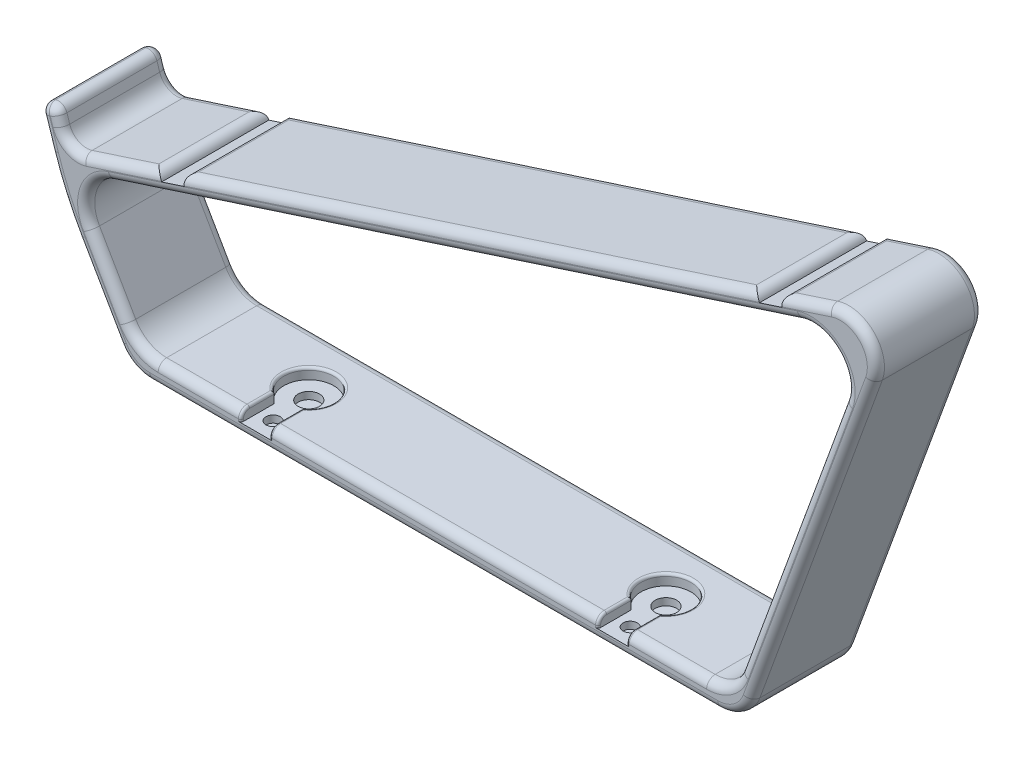
SolidWorks part; units mm, degrees
ref_plane "Front Plane" through (0, 0, 0) normal (0, 0, 1) x (1, 0, 0)
ref_plane "Top Plane" through (0, 0, 0) normal (0, 1, 0) x (1, 0, 0)
ref_plane "Right Plane" through (0, 0, 0) normal (1, 0, 0) x (0, 0, -1)
ref_axis "X Axis" through (0, 0, -132.1637) along (0, 0, 1)
ref_axis "Z Axis" through (0, -24.397, 0) along (0, 1, 0)
ref_axis "Y Axis" through (133.8141, 0, 0) along (-1, 0, 0)
sketch "Sketch13" plane through (0, 0, 0) normal (0, 0, 1) x (1, 0, 0)
  line L0 (-98.9778, 0) -> (72.8295, 0)
  line L1 (72.8295, 0) -> (116.5059, 120)
  line L2 (116.5059, 120) -> (-116.5059, 44.3)
  line L3 (-116.5059, 44.3) -> (-119.5957, 53.8107)
  line L4 (-119.5957, 53.8107) -> (-124.3511, 52.2658)
  line L5 (-124.3511, 52.2658) -> (-118.1715, 33.2444)
  line L6 (-118.1715, 33.2444) -> (-98.9778, 0)
  line L7 (-115.8657, 39.2507) -> (108.3014, 112.0773)
  line L8 (108.3014, 112.0773) -> (69.6924, 6)
  line L9 (69.6924, 6) -> (-96.6684, 6)
  line L10 (-96.6684, 6) -> (-115.8657, 39.2507)
  line L11 (-8.8901, 79.2618) -> (-7.3452, 74.5065) construction
  line L12 (92.7283, 69.2907) -> (97.4268, 67.5806) construction
  line L13 (33.746, 6) -> (33.746, 0) construction
  line L14 (-110.3349, 19.671) -> (-106.0047, 22.171) construction
  line L15 (116.5059, 120) -> (116.5059, 0) construction
  line L16 (116.5059, 0) -> (72.8295, 0) construction
  line L17 (-116.5059, 44.3) -> (-116.5059, 0) construction
  line L18 (-116.5059, 0) -> (-98.9778, 0) construction
  line L19 (-116.5059, 0) -> (-116.5059, -10.091) construction
  line L20 (-116.5059, -10.091) -> (116.5059, -10.091) construction
  line L21 (116.5059, -10.091) -> (116.5059, 0) construction
  line L22 (0, -10.091) -> (0, 0) construction
  dimension "D2" = 245
  dimension "D3" = 5
  dimension "D4" = 5
  dimension "D5" = 5
  dimension "D6" = 6
  dimension "D7" = 44.3
  dimension "D8" = 120
  dimension "D9" = 110
  dimension "D10" = 5
  dimension "D11" = 120
  dimension "D12" = 10
  dimension "D13" = 20
extrude "Boss-Extrude1" add sketch "Sketch13" along normal blind 30
fillet "Fillet1" radius 10 7 edges at (116.5059, 120, 15) (108.3014, 112.0773, 15) (-115.8657, 39.2507, 15) (-98.9778, 0, 15) (-96.6684, 6, 15) (72.8295, 0, 15) (69.6924, 6, 15)
fillet "Fillet2" radius 90 1 edges at (-118.1715, 33.2444, 15)
fillet "Fillet3" radius 2.5 2 edges at (-119.5957, 53.8107, 15) (-124.3511, 52.2658, 15)
fillet "Fillet4" radius 5 1 edges at (-116.5059, 44.3, 15)
fillet "Fillet6" radius 2.4 42 edges at (68.4261, 7.8085, 0) (-14.1023, 6, 0) (-95.8949, 7.3397, 0) (-104.6231, 19.7779, 0) (-110.3665, 37.1397, 0) (-7.659, 74.4045, 0) (99.0859, 103.1784, 0) (86.6883, 52.6958, 0) (-122.3367, 46.0654, 0) (-117.7184, 33.4461, 0) (-107.6527, 15.0254, 0) (-98.2043, 1.3397, 0) (-13.6884, 0, 0) (71.5632, 1.8085, 0) (92.3591, 53.6571, 0) (107.2904, 111.1011, 0) (-7.3717, 79.7551, 0) (-115.5656, 46.1453, 0) (-118.437, 50.2442, 0) (-120.0659, 52.888, 0) (-123.4284, 51.7956, 0) (-95.8949, 7.3397, 30) (-14.1023, 6, 30) (68.4261, 7.8085, 30) (86.6883, 52.6958, 30) (99.0859, 103.1784, 30) (-7.659, 74.4045, 30) (-110.3665, 37.1397, 30) (-104.6231, 19.7779, 30) (107.2904, 111.1011, 30) (92.3591, 53.6571, 30) (71.5632, 1.8085, 30) (-13.6884, 0, 30) (-98.2043, 1.3397, 30) (-107.6527, 15.0254, 30) (-117.7184, 33.4461, 30) (-122.3367, 46.0654, 30) (-123.4284, 51.7956, 30) (-120.0659, 52.888, 30) (-118.437, 50.2442, 30) (-115.5656, 46.1453, 30) (-7.3717, 79.7551, 30)
sketch "Sketch17" plane through (0, 0, 0) normal (0, -1, 0) x (1, 0, 0)
  line L0 (-13.6884, 27.6) -> (-13.6884, 2.4) construction
  line L1 (65.8274, 27.6) -> (-93.2043, 27.6) construction
  line L2 (-93.2043, 2.4) -> (65.8274, 2.4) construction
  line L3 (-79.4543, 15) -> (52.0774, 15) construction
  line L4 (-93.2043, 27.6) -> (-93.2043, 2.4) construction
  line L5 (-89.4543, 2.5) -> (-69.4543, 2.5)
  line L6 (-89.4543, 2.5) -> (-89.4543, 27.5)
  line L7 (-89.4543, 27.5) -> (-69.4543, 27.5)
  line L8 (-69.4543, 2.5) -> (-69.4543, 27.5)
  line L9 (-89.4543, 2.5) -> (-69.4543, 27.5) construction
  line L10 (-89.4543, 27.5) -> (-69.4543, 2.5) construction
  line L11 (42.0774, 2.5) -> (62.0774, 2.5)
  line L12 (42.0774, 2.5) -> (42.0774, 27.5)
  line L13 (42.0774, 27.5) -> (62.0774, 27.5)
  line L14 (62.0774, 2.5) -> (62.0774, 27.5)
  line L15 (42.0774, 2.5) -> (62.0774, 27.5) construction
  line L16 (42.0774, 27.5) -> (62.0774, 2.5) construction
  point P8 (-13.6884, 15)
  point P9 (-13.6884, 15)
  dimension "D1" = 20
  dimension "D2" = 25
  dimension "D3" = 3.75
extrude "Cut-Extrude4" cut sketch "Sketch17" against normal blind 1
sketch "Sketch15" plane through (-24.1407, 74.3073, 0) normal (-0.309, 0.9511, 0) x (0.9511, 0.309, 0)
  line L0 (-97.1173, -2.4) -> (-97.1173, -27.6) construction
  line L1 (-97.1173, -15) -> (-66.6173, -15) construction
  line L2 (127.3807, -30) -> (-92.1173, -30) construction
  line L3 (-69.9673, -30) -> (-63.2673, -30)
  line L4 (-69.9673, -30) -> (-69.9673, 0)
  line L5 (-69.9673, 0) -> (-63.2673, 0)
  line L6 (-63.2673, -30) -> (-63.2673, 0)
  line L7 (-69.9673, -30) -> (-63.2673, 0) construction
  line L8 (-69.9673, 0) -> (-63.2673, -30) construction
  line L9 (-66.6173, -15) -> (109.3827, -15) construction
  line L10 (-92.1173, 0) -> (127.3807, 0) construction
  line L11 (106.0327, -30) -> (112.7327, -30)
  line L12 (106.0327, -30) -> (106.0327, 0)
  line L13 (106.0327, 0) -> (112.7327, 0)
  line L14 (112.7327, -30) -> (112.7327, 0)
  line L15 (106.0327, -30) -> (112.7327, 0) construction
  line L16 (106.0327, 0) -> (112.7327, -30) construction
  dimension "D1" = 30.5
  dimension "D2" = 6.7
  dimension "D3" = 176
extrude "Cut-Extrude2" cut sketch "Sketch15" against normal blind 2.5
sketch "Sketch16" plane through (0, 0, 30) normal (0, 0, 1) x (1, 0, 0)
  line L0 (74.326, 106.2968) -> (75.0985, 103.9191) construction
  line L1 (-84.3122, 54.759) -> (76.7037, 107.0692) construction
  line L2 (75.0985, 103.9191) -> (77.4761, 104.6915) construction
  line L4 (-104.8621, 45.349) -> (88.061, 108.0252) construction
  line L5 (74.326, 106.2968) -> (76.7037, 107.0692)
  line L6 (76.7037, 107.0692) -> (77.4761, 104.6915)
  line L7 (77.4761, 104.6915) -> (83.8483, 106.7617) construction
  line L8 (80.6622, 105.7266) -> (79.8796, 108.1354) construction
  line L9 (83.0758, 109.1394) -> (83.8483, 106.7617)
  line L10 (85.4535, 109.9118) -> (83.0758, 109.1394)
  line L11 (-83.5398, 52.3813) -> (77.4761, 104.6915) construction
  line L12 (-3.0318, 78.5364) -> (-5.2501, 85.3645) construction
  line L13 (-90.6844, 52.6888) -> (-89.9119, 50.3111)
  line L14 (-93.0621, 51.9163) -> (-90.6844, 52.6888)
  line L15 (-81.9346, 55.5314) -> (-84.3122, 54.759)
  line L16 (-84.3122, 54.759) -> (-83.5398, 52.3813)
  arc A0 (74.326, 106.2968) -> (77.4761, 104.6915) centre (75.0985, 103.9191) cw
  arc A1 (85.4535, 109.9118) -> (83.8483, 106.7617) centre (86.226, 107.5341) ccw
  arc A2 (-93.0621, 51.9163) -> (-89.9119, 50.3111) centre (-92.2896, 49.5387) cw
  arc A3 (-81.9346, 55.5314) -> (-83.5398, 52.3813) centre (-81.1621, 53.1537) ccw
  dimension "D1" = 2.5
extrude "Cut-Extrude3" cut sketch "Sketch16" against normal up to surface (30 mm away) up to face at (-33.182, 55.8128, 0)
sketch "Sketch14" plane through (0, 6, 0) normal (0, 1, 0) x (1, 0, 0)
  line L0 (-13.7, 0) -> (-13.7, -30) construction
  line L1 (-90.8949, -30) -> (62.6903, -30) construction
  line L2 (-63.7, -15) -> (36.3, -15) construction
  line L8 (-67.7, -20.7446) -> (-67.7, -30)
  line L9 (-59.7, -20.7446) -> (-59.7, -30)
  line L10 (-63.7, -25) -> (-63.7, -30) construction
  line L11 (-67.7, -25.3723) -> (-59.7, -25.3723) construction
  line L12 (62.6903, -30) -> (-90.8949, -30) construction
  line L13 (-59.7, -30) -> (-67.7, -30)
  line L14 (32.3, -20.7446) -> (32.3, -30)
  line L15 (32.3, -30) -> (40.3, -30)
  line L16 (40.3, -20.7446) -> (40.3, -30)
  line L29 (-13.7, 0) -> (0, 0) construction
  arc A0 (-59.7, -20.7446) -> (-67.7, -20.7446) centre (-63.7, -15) ccw
  arc A1 (32.3, -20.7446) -> (40.3, -20.7446) centre (36.3, -15) cw
  point P7 (-13.7, -15)
  point P17 (-63.7, -25.3723)
  line M35 (-90.8949, -27.6) -> (62.6903, -27.6)
  dimension "D3" = 14
  dimension "D1" = 0
  dimension "D2" = 13.7
  dimension "D4" = 100
  dimension "D5" = 30
  dimension "D6" = 8
  dimension "D8" = 8
extrude "Cut-Extrude1" cut sketch "Sketch14" against normal blind 3 contours L16 L14 L15 M35 | A1 L14 L16 M35 | L13 L9 L8 M35 | L9 A0 L8 M35 | A0 L8 L13 L9 region at (-63.7, 6, 17.2796) region at (36.3, 6, 17.2796) region at (36.3, 6, 28.8) region at (-63.7, 6, 28.8)
sketch "Sketch18" plane through (0, 3, 0) normal (0, 1, 0) x (1, 0, 0)
  line L0 (-63.7, -15) -> (-63.7, -25) construction
  line L1 (-63.7, -15) -> (36.3, -15) construction
  line L2 (-13.7, -15) -> (-13.7, -26.3489) construction
  circle A0 centre (-63.7, -15) radius 3
  circle A2 centre (-63.7, -25) radius 2
  circle A3 centre (36.3, -25) radius 2
  circle A4 centre (36.3, -15) radius 3
  dimension "D1" = 6
  dimension "D2" = 4
  dimension "D3" = 10
extrude "Cut-Extrude5" cut sketch "Sketch18" against normal blind 2
fillet "Fillet5" radius 0.7 14 edges at (40.3, 6, 24.1723) (40.3, 3.3, 30) (40.3, 5.2971, 29.2971) (32.3, 3.3, 30) (32.3, 5.2971, 29.2971) (-59.7, 3.3, 30) (-59.7, 5.2971, 29.2971) (-67.7, 3.3, 30) (-67.7, 5.2971, 29.2971) (32.3, 6, 24.1723) (36.3, 6, 8) (-59.7, 6, 24.1723) (-67.7, 6, 24.1723) (-63.7, 6, 8)
